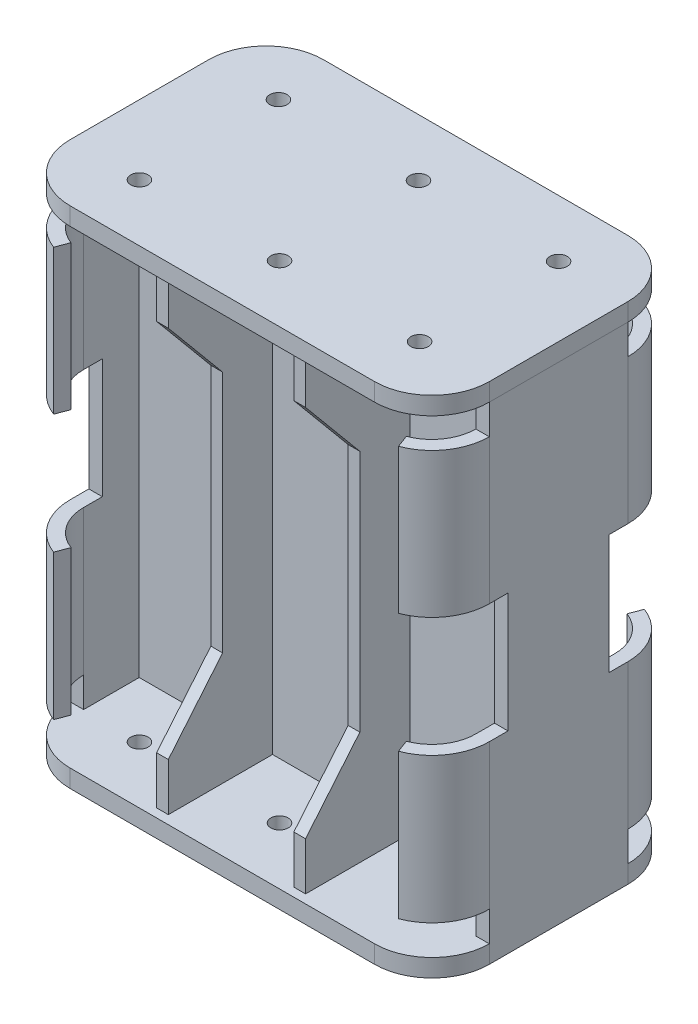
SolidWorks part; units mm, degrees
ref_plane "Front Plane" through (0, 0, 0) normal (0, 0, 1) x (1, 0, 0)
ref_plane "Top Plane" through (0, 0, 0) normal (0, 1, 0) x (1, 0, 0)
ref_plane "Right Plane" through (0, 0, 0) normal (1, 0, 0) x (0, 0, -1)
sketch "Sketch1" plane through (0, 0, 0) normal (0, 1, 0) x (1, 0, 0)
  line L0 (6.6, 0) -> (41.65, 0)
  line L1 (6.6, -29.15) -> (41.65, -29.15)
  line L2 (0, -6.6) -> (0, -22.55)
  line L3 (48.25, -6.6) -> (48.25, -22.55)
  line L4 (0, 0) -> (48.25, 0) construction
  line L5 (0, -29.15) -> (48.25, -29.15) construction
  arc A0 (6.6, 0) -> (0, -6.6) centre (6.6, -6.6) ccw
  arc A1 (6.6, -29.15) -> (0, -22.55) centre (6.6, -22.55) cw
  arc A2 (41.65, -29.15) -> (48.25, -22.55) centre (41.65, -22.55) ccw
  arc A3 (41.65, 0) -> (48.25, -6.6) centre (41.65, -6.6) cw
  point P8 (0, 0)
  dimension "D1" = 6.6
extrude "Boss-Extrude1" add sketch "Sketch1" along normal blind 2.05
sketch "Sketch2" plane through (0, 2.05, 0) normal (0, 1, 0) x (1, 0, 0)
  line L0 (16.9, -13) -> (31.35, -13)
  line L2 (1.55, -13) -> (15.55, -13)
  line L4 (31.35, 0) -> (32.7, 0)
  line L5 (16.9, 0) -> (16.9, -13)
  line L6 (31.35, 0) -> (31.35, -13)
  line L7 (32.7, 0) -> (32.7, -13)
  line L8 (15.55, 0) -> (15.55, -13)
  line L9 (46.7, -6.6) -> (46.7, -13)
  line L10 (1.55, -6.6) -> (1.55, -13)
  line L11 (0, -6.6) -> (0, -13)
  line L12 (48.25, -6.6) -> (48.25, -13)
  line L14 (1.55, 0) -> (1.55, -13) construction
  line L15 (15.55, 0) -> (16.9, 0)
  line L16 (4.8204, -1.874) -> (4.2742, -0.4234)
  line L17 (43.4296, -1.874) -> (43.9758, -0.4234)
  line L18 (46.7, 0) -> (46.7, -13) construction
  line L20 (43.4296, -27.276) -> (43.9758, -28.7266)
  line L21 (4.8204, -27.276) -> (4.2742, -28.7266)
  line L22 (15.55, -29.15) -> (16.9, -29.15)
  line L23 (48.25, -22.55) -> (48.25, -16.15)
  line L24 (0, -22.55) -> (0, -16.15)
  line L25 (1.55, -22.55) -> (1.55, -16.15)
  line L26 (46.7, -22.55) -> (46.7, -16.15)
  line L27 (15.55, -29.15) -> (15.55, -16.15)
  line L28 (32.7, -29.15) -> (32.7, -16.15)
  line L29 (31.35, -29.15) -> (31.35, -16.15)
  line L30 (16.9, -29.15) -> (16.9, -16.15)
  line L31 (31.35, -29.15) -> (32.7, -29.15)
  line L32 (1.55, -16.15) -> (15.55, -16.15)
  line L33 (0, -13) -> (0, -16.15)
  line L34 (48.25, -13) -> (48.25, -16.15)
  line L35 (16.9, -16.15) -> (31.35, -16.15)
  line L36 (32.7, -13) -> (46.7, -13)
  line L37 (32.7, -16.15) -> (46.7, -16.15)
  arc A0 (4.2742, -0.4234) -> (0, -6.6) centre (6.6, -6.6) ccw
  arc A1 (4.8204, -1.874) -> (1.55, -6.6) centre (6.6, -6.6) ccw
  arc A2 (48.25, -6.6) -> (43.9758, -0.4234) centre (41.65, -6.6) ccw
  arc A3 (46.7, -6.6) -> (43.4296, -1.874) centre (41.65, -6.6) ccw
  arc A4 (46.7, -22.55) -> (43.4296, -27.276) centre (41.65, -22.55) cw
  arc A5 (6.6, -1.55) -> (1.55, -6.6) centre (6.6, -6.6) ccw construction
  arc A6 (6.6, 0) -> (0, -6.6) centre (6.6, -6.6) ccw construction
  arc A7 (46.7, -6.6) -> (41.65, -1.55) centre (41.65, -6.6) ccw construction
  arc A8 (48.25, -6.6) -> (41.65, 0) centre (41.65, -6.6) ccw construction
  arc A9 (48.25, -22.55) -> (43.9758, -28.7266) centre (41.65, -22.55) cw
  arc A10 (4.8204, -27.276) -> (1.55, -22.55) centre (6.6, -22.55) cw
  arc A11 (4.2742, -28.7266) -> (0, -22.55) centre (6.6, -22.55) cw
  point P0 (0, 0)
  point P1 (48.25, 0)
extrude "Boss-Extrude2" add sketch "Sketch2" along normal blind 54
extrude "Boss-Extrude9" add sketch "Sketch1<6>" along normal blind 2.05 from offset 56.05 separate body
sketch "Sketch1<6>" plane through (0, 0, 0) normal (0, 1, 0) x (1, 0, 0) same geometry as "Sketch1"
sketch "Sketch3" plane through (48.25, 0, 0) normal (1, 0, 0) x (0, 0, -1)
  line L0 (-6.6, 56.05) -> (-6.6, 52.6)
  line L1 (-6.6, 56.05) -> (-6.6, 0) construction
  line L2 (-6.6, 52.6) -> (7.4299, 52.6)
  line L3 (7.4299, 52.6) -> (10.8799, 56.05)
  line L4 (10.8799, 56.05) -> (-6.6, 56.05)
  line L5 (-14.575, 35.95) -> (-14.575, 20.1586) construction
  line L6 (14.8636, 35.95) -> (14.8636, 22.2)
  line L7 (-8.75, 35.95) -> (14.8636, 35.95)
  line L8 (10.8799, 2.05) -> (-6.6, 2.05)
  line L9 (7.4299, 5.5) -> (10.8799, 2.05)
  line L10 (-6.6, 5.5) -> (7.4299, 5.5)
  line L11 (-6.6, 2.05) -> (-6.6, 5.5)
  line L12 (-22.55, 2.05) -> (-22.55, 5.5)
  line L13 (-22.55, 5.5) -> (-36.5799, 5.5)
  line L14 (-36.5799, 5.5) -> (-40.0299, 2.05)
  line L15 (-40.0299, 2.05) -> (-22.55, 2.05)
  line L16 (-40.0299, 56.05) -> (-22.55, 56.05)
  line L17 (-36.5799, 52.6) -> (-40.0299, 56.05)
  line L18 (-22.55, 52.6) -> (-36.5799, 52.6)
  line L19 (-22.55, 56.05) -> (-22.55, 52.6)
  line L20 (14.8636, 22.2) -> (-8.75, 22.2)
  line L21 (-8.75, 35.95) -> (-8.75, 22.2)
  line L22 (-20.4, 22.2) -> (-42.8232, 22.2)
  line L23 (-42.8232, 22.2) -> (-44.0136, 35.95)
  line L25 (-20.4, 35.95) -> (-20.4, 22.2)
  line L26 (-20.4, 35.95) -> (-44.0136, 35.95)
extrude "Cut-Extrude2" cut sketch "Sketch3" against normal blind 12.5
extrude "Cut-Extrude4" cut sketch "Sketch3<2>" against normal blind 12.5 from offset 40 offset against normal yes
sketch "Sketch3<2>" plane through (48.25, 0, 0) normal (1, 0, 0) x (0, 0, -1) same geometry as "Sketch3"
sketch "Sketch4" plane through (16.9, 0, 0) normal (1, 0, 0) x (0, 0, -1)
  line L0 (-29.15, 2.05) -> (-28.15, 2.05)
  line L1 (-29.15, 2.05) -> (-16.15, 2.05) construction
  line L2 (-28.15, 2.05) -> (-28.15, 7.55)
  line L3 (-28.15, 7.55) -> (-21.9, 15.05)
  line L5 (-21.9, 15.05) -> (-21.9, 43.05)
  line L6 (-21.9, 29.05) -> (-29.15, 29.05) construction
  line L7 (-29.15, 2.05) -> (-29.15, 56.05)
  line L8 (-28.15, 50.55) -> (-21.9, 43.05)
  line L9 (-28.15, 56.05) -> (-28.15, 50.55)
  line L10 (-29.15, 56.05) -> (-28.15, 56.05)
  line L11 (-7.25, 29.05) -> (0, 29.05) construction
  line L13 (-14.575, 9.2823) -> (-14.575, 37.9886) construction
  line L14 (0, 56.05) -> (-1, 56.05)
  line L15 (-1, 56.05) -> (-1, 50.55)
  line L16 (-1, 50.55) -> (-7.25, 43.05)
  line L17 (0, 2.05) -> (0, 56.05)
  line L18 (-7.25, 15.05) -> (-7.25, 43.05)
  line L19 (-1, 7.55) -> (-7.25, 15.05)
  line L20 (-1, 2.05) -> (-1, 7.55)
  line L21 (0, 2.05) -> (-1, 2.05)
extrude "Cut-Extrude5" cut sketch "Sketch4" against normal blind 5 and the other way blind 22.5
sketch "Sketch8" plane through (0, 58.1, 0) normal (0, 1, 0) x (1, 0, 0)
  circle A0 centre (8, -6.575) radius 1
  circle A1 centre (24.125, -6.575) radius 1
  circle A2 centre (40.25, -6.575) radius 1
  circle A3 centre (40.25, -22.575) radius 1
  circle A4 centre (24.125, -22.575) radius 1
  circle A5 centre (8, -22.575) radius 1
extrude "Cut-Extrude6" cut sketch "Sketch8" against normal blind 85
